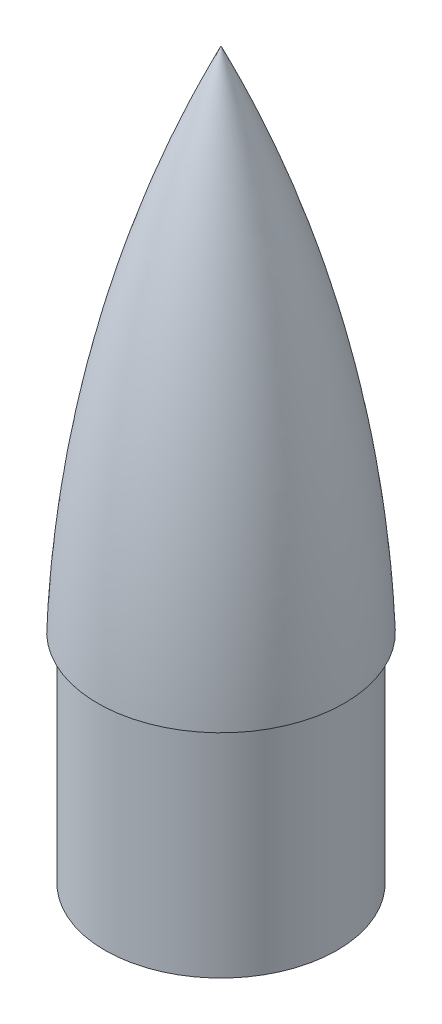
SolidWorks part; units mm, degrees
ref_plane "Спереди" through (0, 0, 0) normal (0, 0, 1) x (1, 0, 0)
ref_plane "Сверху" through (0, 0, 0) normal (0, 1, 0) x (1, 0, 0)
ref_plane "Справа" through (0, 0, 0) normal (1, 0, 0) x (0, 0, -1)
sketch "Эскиз1" plane through (0, 0, 0) normal (0, 1, 0) x (1, 0, 0)
  circle A0 centre (0, 0) radius 15
  circle A1 centre (0, 0) radius 16
  dimension "D1" = 32
  dimension "D2" = 30
extrude "Бобышка-Вытянуть1" add sketch "Эскиз1" along normal blind 30
sketch "Эскиз5" plane through (0, 0, 0) normal (0, 0, 1) x (1, 0, 0)
  line L0 (0, 100) -> (0, 0) construction
  line L2 (0, 30) -> (-17, 30)
  line L3 (16, 30) -> (-16, 30) construction
  line L7 (0, 100) -> (0, 30)
  arc A0 (0, 100) -> (-17, 30) centre (162.9033, 23.3735) ccw
  dimension "D1" = 100
revolve "Повернуть1" add sketch "Эскиз5" angle 360 about L0
sketch "Эскиз6" plane through (0, 0, 0) normal (0, 0, 1) x (1, 0, 0)
  line L1 (0, 98) -> (0, 30)
  line L2 (0, 30) -> (-17, 30) construction
  line L3 (-17, 30) -> (17, 30) construction
  line L9 (0, 100) -> (0, 30) construction
  line L13 (0, 30) -> (-14.9986, 30)
  line L15 (0, 98) -> (-5.3831, 81.4485)
  arc A3 (1.8098, 99.1487) -> (-15.0014, 29.9264) centre (162.9033, 23.3735) ccw
  arc A4 (-5.3831, 81.4485) -> (-14.9986, 30) centre (162.9033, 23.3735) ccw
  point P0 (-14.9986, 30)
  point P1 (0, 98)
  dimension "D2" = 2
  dimension "D1" = 2
revolve "Вырез-Повернуть1" cut sketch "Эскиз6" angle 360 about L1
